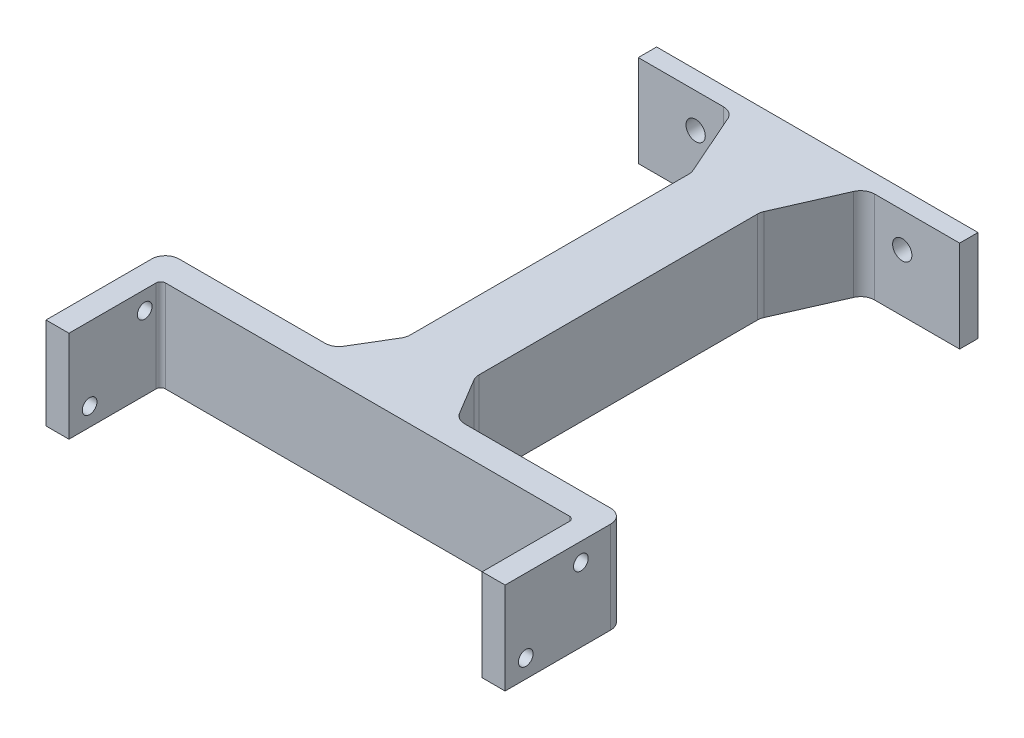
SolidWorks part; units mm, degrees
ref_plane "前视基准面" through (0, 0, 0) normal (0, 0, 1) x (1, 0, 0)
ref_plane "上视基准面" through (0, 0, 0) normal (0, 1, 0) x (1, 0, 0)
ref_plane "右视基准面" through (0, 0, 0) normal (1, 0, 0) x (0, 0, -1)
sketch "草图1" plane through (0, 0, 0) normal (0, 0, 1) x (1, 0, 0)
  line L1 (-27.1107, 16.6861) -> (42.8893, 16.6861)
  line L2 (-27.1107, 16.6861) -> (-27.1107, -3.3139)
  line L3 (-27.1107, -3.3139) -> (42.8893, -3.3139)
  line L4 (42.8893, 16.6861) -> (42.8893, -3.3139)
  dimension "D1" = 70
  dimension "D2" = 20
extrude "凸台-拉伸1" add sketch "草图1" along normal blind 4
sketch "草图2" plane through (0, 0, 4) normal (0, 0, 1) x (1, 0, 0)
  line L0 (42.8893, 16.6861) -> (-27.1107, 16.6861) construction
  line L1 (-27.1107, 16.6861) -> (-27.1107, -3.3139) construction
  line L2 (42.8893, -3.3139) -> (42.8893, 16.6861) construction
  circle A0 centre (-14.6107, 9.1861) radius 2.1
  circle A1 centre (30.3893, 9.1861) radius 2.1
  dimension "D1" = 7.5
  dimension "D2" = 7.5
  dimension "D3" = 12.5
  dimension "D4" = 12.5
  dimension "D5" = 4.2
  dimension "D6" = 4.2
extrude "切除-拉伸1" cut sketch "草图2" against normal blind 4
sketch "草图3" plane through (0, 0, 4) normal (0, 0, 1) x (1, 0, 0)
  line L0 (42.8893, 16.6861) -> (-27.1107, 16.6861) construction
  line L1 (0.3893, 16.6861) -> (15.3893, 16.6861)
  line L2 (0.3893, 16.6861) -> (0.3893, -3.3139)
  line L3 (0.3893, -3.3139) -> (15.3893, -3.3139)
  line L4 (15.3893, 16.6861) -> (15.3893, -3.3139)
  line L5 (-27.1107, -3.3139) -> (42.8893, -3.3139) construction
  line L6 (-27.1107, 16.6861) -> (-27.1107, -3.3139) construction
  dimension "D1" = 15
  dimension "D2" = 27.5
extrude "凸台-拉伸2" add sketch "草图3" along normal blind 88
sketch "草图4" plane through (0, 0, 92) normal (0, 0, 1) x (1, 0, 0)
  line L0 (0.3893, 16.6861) -> (-27.1107, 16.6861) construction
  line L1 (-42.1107, 16.6861) -> (57.8893, 16.6861)
  line L2 (-42.1107, 16.6861) -> (-42.1107, -3.3139)
  line L3 (-42.1107, -3.3139) -> (57.8893, -3.3139)
  line L4 (57.8893, 16.6861) -> (57.8893, -3.3139)
  line L5 (15.3893, -3.3139) -> (42.8893, -3.3139) construction
  line L6 (0.3893, 16.6861) -> (0.3893, -3.3139) construction
  dimension "D1" = 100
  dimension "D2" = 42.5
extrude "凸台-拉伸3" add sketch "草图4" along normal blind 6
sketch "草图5" plane through (0, 0, 98) normal (0, 0, 1) x (1, 0, 0)
  line L0 (-42.1107, -3.3139) -> (57.8893, -3.3139) construction
  line L1 (-42.1107, 16.6861) -> (-37.1107, 16.6861)
  line L2 (-42.1107, 16.6861) -> (-42.1107, -3.3139)
  line L3 (-42.1107, -3.3139) -> (-37.1107, -3.3139)
  line L4 (-37.1107, 16.6861) -> (-37.1107, -3.3139)
  line L5 (57.8893, 16.6861) -> (-42.1107, 16.6861) construction
  line L6 (57.8893, 16.6861) -> (52.8893, 16.6861)
  line L7 (57.8893, 16.6861) -> (57.8893, -3.3139)
  line L8 (57.8893, -3.3139) -> (52.8893, -3.3139)
  line L9 (52.8893, 16.6861) -> (52.8893, -3.3139)
  line L10 (57.8893, -3.3139) -> (57.8893, 16.6861) construction
  dimension "D1" = 5
  dimension "D2" = 5
extrude "凸台-拉伸4" add sketch "草图5" along normal blind 20
sketch "草图6" plane through (-37.1107, 0, 0) normal (1, 0, 0) x (0, 0, -1)
  line L0 (-118, 16.6861) -> (-92, 16.6861) construction
  line L1 (-118, -3.3139) -> (-92, -3.3139) construction
  line L2 (-118, -3.3139) -> (-118, 16.6861) construction
  circle A0 centre (-101.5, 12.6861) radius 1.6
  circle A1 centre (-113.5, 0.6861) radius 1.6
  dimension "D1" = 3.2
  dimension "D2" = 3.2
  dimension "D3" = 4
  dimension "D4" = 4
  dimension "D5" = 12
  dimension "D6" = 4.5
extrude "切除-拉伸2" cut sketch "草图6" along normal up to surface (95 mm away) up to face at (57.8893, 6.6861, 105)
extrude "切除-拉伸3" cut sketch "草图6<2>" against normal blind 20
sketch "草图6<2>" plane through (-37.1107, 0, 0) normal (1, 0, 0) x (0, 0, -1) same geometry as "草图6"
sketch "草图7" plane through (0, -3.3139, 0) normal (0, -1, 0) x (1, 0, 0)
  line L0 (0.3893, 4) -> (0.3893, 19.9004)
  line L1 (0.3893, 92) -> (0.3893, 4) construction
  line L2 (0.3893, 19.9004) -> (-6.6107, 4)
  line L3 (-27.1107, 4) -> (0.3893, 4) construction
  line L4 (-6.6107, 4) -> (0.3893, 4)
  line L5 (15.3893, 4) -> (22.3893, 4)
  line L6 (15.3893, 4) -> (42.8893, 4) construction
  line L7 (22.3893, 4) -> (15.3893, 19.9004)
  line L8 (15.3893, 92) -> (15.3893, 4) construction
  line L9 (15.3893, 19.9004) -> (15.3893, 4)
  dimension "D1" = 7
  dimension "D2" = 7
extrude "凸台-拉伸5" add sketch "草图7" against normal blind 20
sketch "草图8" plane through (0, -3.3139, 0) normal (0, -1, 0) x (1, 0, 0)
  line L0 (-5.6107, 92) -> (0.3893, 82)
  line L1 (-42.1107, 92) -> (0.3893, 92) construction
  line L2 (0.3893, 92) -> (0.3893, 19.9004) construction
  line L3 (0.3893, 82) -> (0.3893, 92)
  line L4 (0.3893, 92) -> (-5.6107, 92)
  line L5 (15.3893, 82) -> (15.3893, 92)
  line L6 (15.3893, 92) -> (15.3893, 19.9004) construction
  line L7 (15.3893, 92) -> (21.3893, 92)
  line L8 (15.3893, 92) -> (57.8893, 92) construction
  line L9 (21.3893, 92) -> (15.3893, 82)
  dimension "D1" = 10
  dimension "D2" = 10
  dimension "D3" = 6
  dimension "D4" = 6
extrude "凸台-拉伸6" add sketch "草图8" against normal blind 20
fillet "圆角1" radius 3 10 edges at (-42.1107, 6.6861, 92) (57.8893, 6.6861, 92) (0.3893, 6.6861, 19.9004) (-6.6107, 6.6861, 4) (22.3893, 6.6861, 4) (15.3893, 6.6861, 19.9004) (21.3893, 6.6861, 92) (15.3893, 6.6861, 82) (0.3893, 6.6861, 82) (-5.6107, 6.6861, 92)
fillet "圆角2" radius 1 2 edges at (-37.1107, 6.6861, 98) (52.8893, 6.6861, 98)
equation "\"、\"=130"
